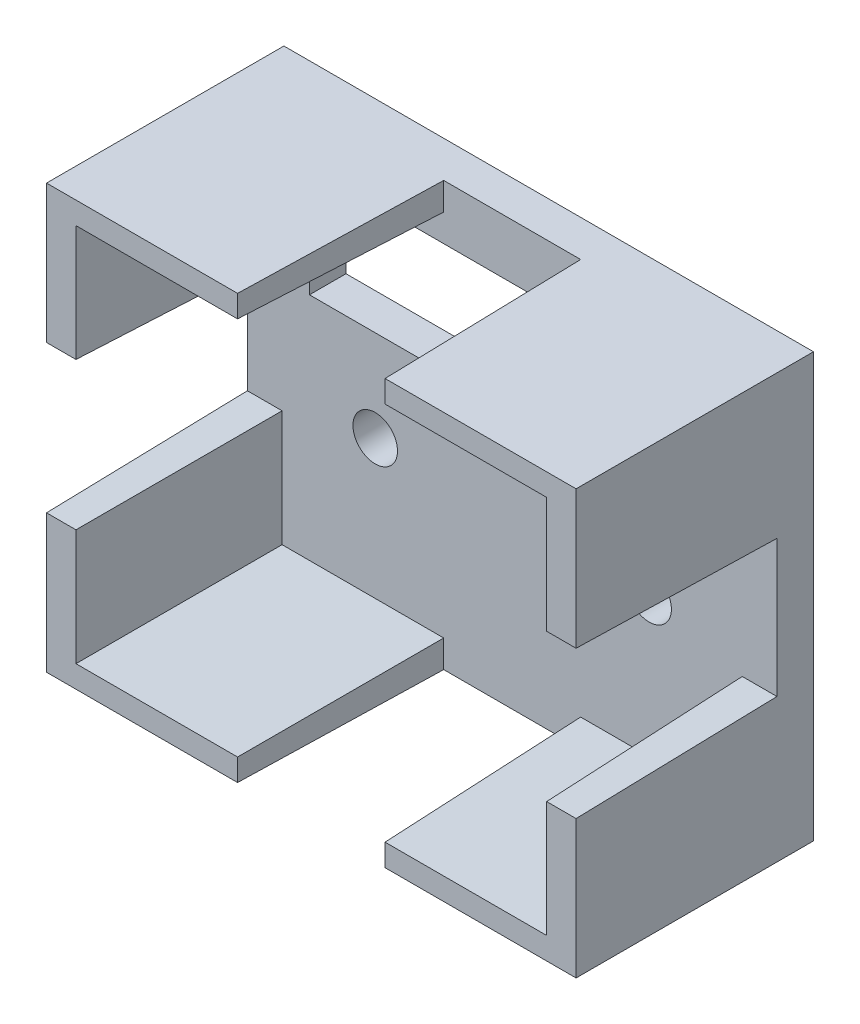
SolidWorks part; units mm, degrees
note: The reader was unsure of these and kept them because the rebuilt part matched: shared geometry of "Sketch2<5>".
ref_plane "Front Plane" through (0, 0, 0) normal (0, 0, 1) x (1, 0, 0)
ref_plane "Top Plane" through (0, 0, 0) normal (0, 1, 0) x (1, 0, 0)
ref_plane "Right Plane" through (0, 0, 0) normal (1, 0, 0) x (0, 0, -1)
sketch "Sketch2" plane through (0, 0, 0) normal (0, 0, 1) x (1, 0, 0)
  line L0 (-16.002, 12.827) -> (-16.002, -12.827)
  line L1 (-18.415, 14.732) -> (18.415, 14.732)
  line L2 (-18.415, 14.732) -> (-18.415, -14.732)
  line L3 (-18.415, -14.732) -> (18.415, -14.732)
  line L4 (18.415, 14.732) -> (18.415, -14.732)
  line L5 (-18.415, 14.732) -> (18.415, -14.732) construction
  line L6 (-18.415, -14.732) -> (18.415, 14.732) construction
  line L7 (-15.875, 12.7) -> (15.875, 12.7) construction
  line L8 (-15.875, 12.7) -> (-15.875, -12.7) construction
  line L9 (-15.875, -12.7) -> (15.875, -12.7) construction
  line L10 (15.875, 12.7) -> (15.875, -12.7) construction
  line L11 (-15.875, 12.7) -> (15.875, -12.7) construction
  line L12 (-15.875, -12.7) -> (15.875, 12.7) construction
  line L13 (-16.002, -12.827) -> (16.002, -12.827)
  line L14 (16.002, 12.827) -> (16.002, -12.827)
  line L15 (-16.002, 12.827) -> (16.002, 12.827)
  line L16 (-9.525, -3.175) -> (9.525, -3.175) construction
  line L17 (18.415, 4.7625) -> (16.002, 4.7625)
  line L18 (-14.097, 10.922) -> (14.097, 10.922)
  line L19 (-14.097, 10.922) -> (-14.097, 3.175)
  line L20 (-14.097, 3.175) -> (14.097, 3.175)
  line L21 (14.097, 10.922) -> (14.097, 3.175)
  line L22 (16.002, -4.7625) -> (18.415, -4.7625)
  line L23 (17.2085, -4.7625) -> (17.2085, 4.7625) construction
  line L24 (4.7625, -14.732) -> (4.7625, -12.827)
  line L25 (-4.7625, -14.732) -> (-4.7625, -12.827)
  line L26 (-16.002, -4.7625) -> (-18.415, -4.7625)
  line L27 (-16.002, 4.7625) -> (-18.415, 4.7625)
  line L28 (4.7625, 12.827) -> (4.7625, 14.732)
  line L29 (-4.7625, 12.827) -> (-4.7625, 14.732)
  line L30 (4.7625, 13.7795) -> (-4.7625, 13.7795) construction
  line L31 (-17.2085, -4.7625) -> (-17.2085, 4.7625) construction
  line L32 (4.7625, -13.7795) -> (-4.7625, -13.7795) construction
  circle A0 centre (-9.525, -3.175) radius 1.55
  circle A1 centre (9.525, -3.175) radius 1.55
  point P0 (0, 0)
  point P6 (0, 0)
  point P19 (0, -3.175)
  point P20 (0, 3.175)
  point P49 (17.2085, 0)
  point P50 (18.415, 0)
  point P51 (-17.2085, 0)
  point P52 (0, 13.7795)
  point P53 (0, -13.7795)
  dimension "D7" = 3.1
  dimension "D1" = 25.4
  dimension "D2" = 31.75
  dimension "D3" = 2.54
  dimension "D5" = 19.05
  dimension "D6" = 9.525
  dimension "D8" = 1.905
  dimension "D9" = 1.905
  dimension "D10" = 6.35
  dimension "D11" = 9.525
  dimension "D4" = 0.127
extrude "Boss-Extrude1" add sketch "Sketch2" along normal blind 16.51 contours L15 L0 L13 L14 | L4 L1 L2 L3 L0 L15 L14 L13 | L24 L3 L4 L22 L14 L13 | L25 L3 L24 L13 | L0 L26 L2 L3 L25 L13 | L0 L27 L2 L26 | L15 L29 L1 L2 L27 L0 | L28 L15 L14 L17 L4 L1 | L14 L22 L4 L17
ref_plane "Plane1" through (0, 0, 2.54) normal (0, 0, -1) x (-1, 0, 0)
extrude "Cut-Extrude1" cut sketch "Sketch2<5>" along normal through all draft 1.5 from surface at 2.54 contours L15 L0 L13 L14 A1 A0 L18 L21 L20 L19 | L14 L22 L4 L17 | L25 L3 L24 L13 | L0 L27 L2 L26 | L29 L15 L28 L1 starting at plane "Plane1" draft outward yes
sketch "Sketch2<5>" plane through (0, 0, 0) normal (0, 0, 1) x (1, 0, 0) same geometry as "Sketch2"
